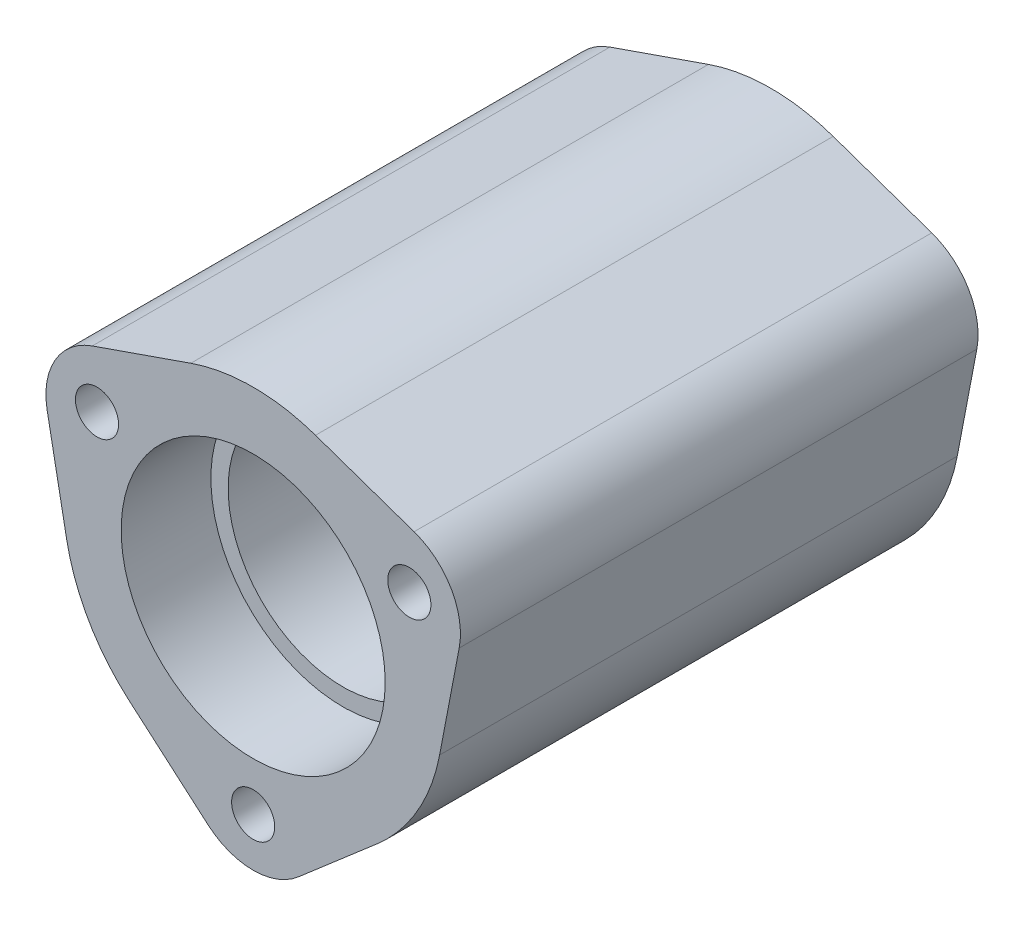
SolidWorks part; units mm, degrees
ref_plane "Спереди" through (0, 0, 0) normal (0, 0, 1) x (1, 0, 0)
ref_plane "Сверху" through (0, 0, 0) normal (0, 1, 0) x (1, 0, 0)
ref_plane "Справа" through (0, 0, 0) normal (1, 0, 0) x (0, 0, -1)
sketch "Эскиз1" plane through (0, 0, 0) normal (0, 0, 1) x (1, 0, 0)
  line L0 (-9.3248, 8.403) -> (-3.6137, 10.3895)
  line L1 (0, 0) -> (0, -9.25) construction
  line L2 (-11.9396, 3.874) -> (-10.8044, -2.0651)
  line L3 (2.6148, -12.277) -> (7.1907, -8.3243)
  line L4 (-2.6148, -12.277) -> (-7.1907, -8.3243)
  line L5 (11.9396, 3.874) -> (10.8044, -2.0651)
  line L6 (9.3248, 8.403) -> (3.6137, 10.3895)
  circle A0 centre (0, 0) radius 11 construction
  arc A1 (7.1907, -8.3243) -> (10.8044, -2.0651) centre (0, 0) ccw
  arc A2 (-9.3248, 8.403) -> (-11.9396, 3.874) centre (-8.0107, 4.625) ccw
  arc A3 (-2.6148, -12.277) -> (2.6148, -12.277) centre (0, -9.25) ccw
  arc A4 (11.9396, 3.874) -> (9.3248, 8.403) centre (8.0107, 4.625) ccw
  arc A5 (3.6137, 10.3895) -> (-3.6137, 10.3895) centre (0, 0) ccw
  arc A6 (-10.8044, -2.0651) -> (-7.1907, -8.3243) centre (0, 0) ccw
  circle A7 centre (0, 0) radius 9.25 construction
  point P2 (0, 0)
  point P24 (0, 0)
  dimension "D1" = 4
  dimension "D2" = 22
  dimension "D3" = 3
  dimension "D4" = 18.5
extrude "тело" add sketch "Эскиз1" along normal blind 15 and the other way blind 15
sketch "Эскиз2" plane through (0, 0, 15) normal (0, 0, 1) x (1, 0, 0)
  circle A0 centre (0, 0) radius 7.65
  dimension "D1" = 15.3
extrude "углубление под подшипник" cut sketch "Эскиз2" against normal blind 5.2
mirror "Углубление под подшипник с обратной стороны" about plane through (0, 0, 0) normal (0, 0, 1) of "углубление под подшипник"
sketch "Эскиз3" plane through (0, 0, 9.8) normal (0, 0, 1) x (1, 0, 0)
  circle A0 centre (0, 0) radius 6.65
  circle A1 centre (0, 0) radius 7.65 construction
  dimension "D1" = 1
extrude "сквозное отверстие" cut sketch "Эскиз3" against normal through all
sketch "Эскиз4" plane through (0, 0, 15) normal (0, 0, 1) x (1, 0, 0)
  line L0 (0, -13.25) -> (0, -7.65) construction
  circle A0 centre (-9.05, 5.225) radius 1.25
  circle A1 centre (0, -10.45) radius 1.25
  circle A2 centre (9.05, 5.225) radius 1.25
  arc A3 (-2.6148, -12.277) -> (2.6148, -12.277) centre (0, -9.25) ccw construction
  circle A4 centre (0, 0) radius 7.65 construction
  point P8 (0, 0)
  point P16 (0, -11.2482)
  point P17 (0, 0)
  point P18 (0, -10.45)
  dimension "D1" = 2.5
  dimension "D2" = 3
extrude "отверстия для шурупов" cut sketch "Эскиз4" against normal through all
